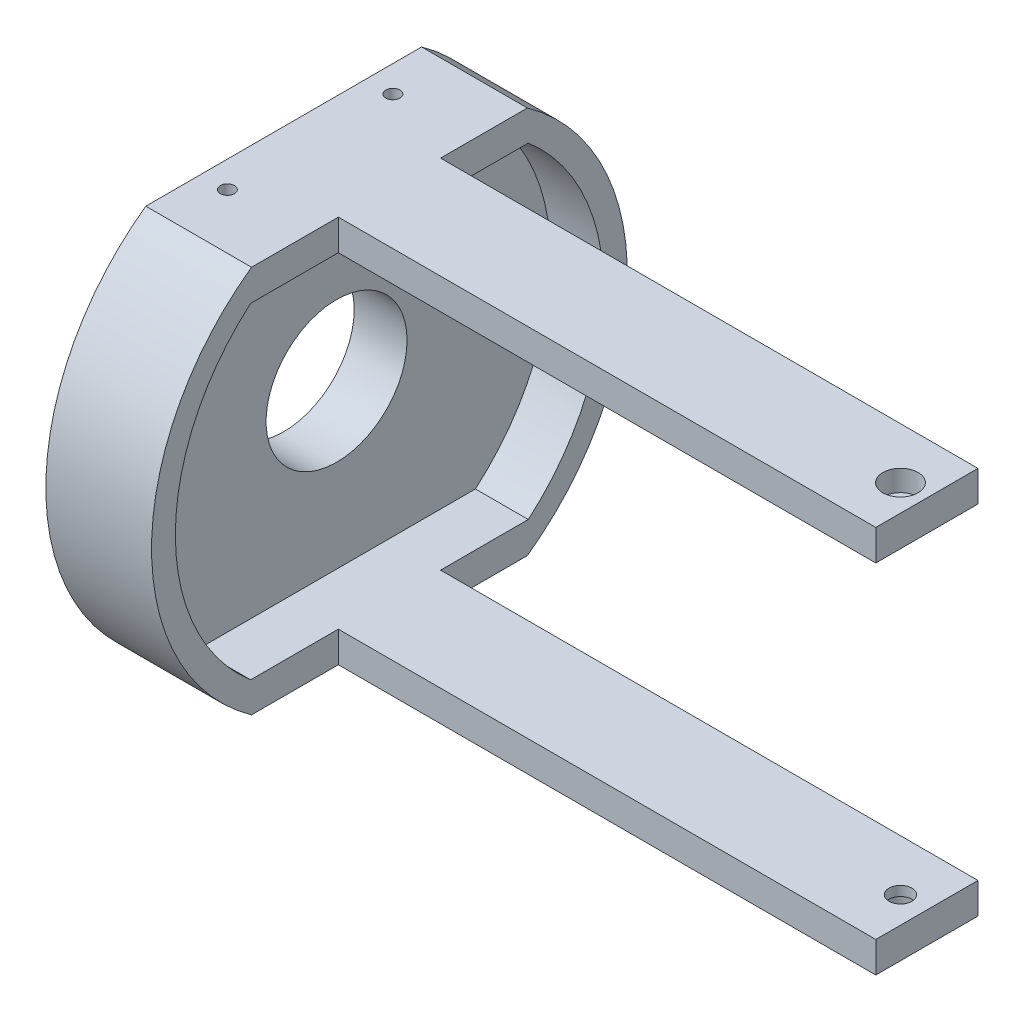
SolidWorks part; units mm, degrees
note: The reader was unsure of these and kept them because the rebuilt part matched: shared geometry of "草图3<4>", "草图3<5>", "草图3<6>".
ref_plane "前视基准面" through (0, 0, 0) normal (0, 0, 1) x (1, 0, 0)
ref_plane "上视基准面" through (0, 0, 0) normal (0, 1, 0) x (1, 0, 0)
ref_plane "右视基准面" through (0, 0, 0) normal (1, 0, 0) x (0, 0, -1)
other "Configuration Table"
sketch "草图1" plane through (0, 0, 0) normal (1, 0, 0) x (0, 0, -1)
  line L5 (-13.5, -11) -> (13.5, -11)
  line L6 (-13.5, -11) -> (-13.5, 11)
  line L7 (-13.5, 11) -> (13.5, 11)
  line L8 (13.5, -11) -> (13.5, 11)
  line L9 (-13.5, -11) -> (13.5, 11) construction
  line L10 (-13.5, 11) -> (13.5, -11) construction
  circle A0 centre (0, 0) radius 13.5
  circle A3 centre (0, 0) radius 4
  point P0 (0, 0)
  dimension "D1" = 27
  dimension "D6" = 8
  dimension "D3" = 22
extrude "凸台-拉伸1" add sketch "草图1" along normal blind 3 contours L7 A0 L5 A3
sketch "草图2" plane through (3, 0, 0) normal (1, 0, 0) x (0, 0, -1)
  line L1 (-12.15, -9.25) -> (12.15, -9.25)
  line L2 (-12.15, -9.25) -> (-12.15, 9.25)
  line L3 (-12.15, 9.25) -> (12.15, 9.25)
  line L4 (12.15, -9.25) -> (12.15, 9.25)
  line L5 (-12.15, -9.25) -> (12.15, 9.25) construction
  line L6 (-12.15, 9.25) -> (12.15, -9.25) construction
  circle A0 centre (0, 0) radius 12.15
  arc M7 (7.8262, -11) -> (7.8262, 11) centre (0, 0) ccw
  line M8 (7.8262, 11) -> (-7.8262, 11)
  arc M9 (-7.8262, 11) -> (-7.8262, -11) centre (0, 0) ccw
  line M10 (-7.8262, -11) -> (7.8262, -11)
  dimension "D1" = 24.3
  dimension "D2" = 18.5
extrude "凸台-拉伸2" add sketch "草图2" along normal blind 3 contours L3 A0 M8 | A0 L3 M8 M9 | A0 L3 L2 M9 | L2 M9 | A0 L2 L1 M9 | A0 L1 M9 M10 | L1 A0 M10 | A0 L1 M10 M7 | A0 L1 L4 M7 | L4 M7 | A0 L4 L3 M7 | A0 L3 M7 M8
sketch "草图3" plane through (0, 11, 0) normal (0, 1, 0) x (1, 0, 0)
  line L0 (0, -7.8262) -> (0, 7.8262) construction
  line L1 (0, -2.9) -> (36.5, -2.9)
  line L2 (0, -2.9) -> (0, 2.9)
  line L3 (0, 2.9) -> (36.5, 2.9)
  line L4 (36.5, -2.9) -> (36.5, 2.9)
  circle A0 centre (35, 0) radius 0.65
  circle A1 centre (35, 0) radius 1
  point P10 (0, 0)
  dimension "D3" = 1.3
  dimension "D4" = 2
  dimension "D1" = 5.8
  dimension "D2" = 36.5
extrude "凸台-拉伸3" add sketch "草图3" against normal up to surface (1.75 mm away) contours L3 L4 L1 L2 | A0 up to face at (4.5, 9.25, 0)
extrude "切除-拉伸1" cut sketch "草图3<4>" against normal blind 1.2 contours A1
sketch "草图3<4>" plane through (0, 11, 0) normal (0, 1, 0) x (1, 0, 0) same geometry as "草图3"
extrude "凸台-拉伸4" add sketch "草图3<5>" against normal up to surface (1.75 mm away) from surface contours L4 L3 L2 L1 | A0
sketch "草图3<5>" plane through (0, 11, 0) normal (0, 1, 0) x (1, 0, 0) same geometry as "草图3"
extrude "切除-拉伸2" cut sketch "草图3<6>" along normal blind 1.2 from surface at -22 contours A1 starting at face at (12.125, -11, 0)
sketch "草图3<6>" plane through (0, 11, 0) normal (0, 1, 0) x (1, 0, 0) same geometry as "草图3"
sketch "草图5" plane through (0, 11, 0) normal (0, 1, 0) x (1, 0, 0)
  line L1 (0, -7.8262) -> (0, 7.8262) construction
  line L2 (1.5, -7.8262) -> (1.5, -4.6957) construction
  line L3 (6, -7.8262) -> (0, -7.8262) construction
  line L4 (1.5, -4.6957) -> (1.5, -1.5652) construction
  line L5 (1.5, -1.5652) -> (1.5, 1.5652) construction
  line L6 (1.5, 4.6957) -> (1.5, 7.8262) construction
  line L7 (6, 7.8262) -> (0, 7.8262) construction
  line L8 (1.5, 1.5652) -> (1.5, 4.6957) construction
  circle A0 centre (1.5, -4.6957) radius 0.4
  circle A1 centre (1.5, 4.6957) radius 0.4
  dimension "D2" = 0.8
  dimension "D1" = 1.5
extrude "切除-拉伸3" cut sketch "草图5" against normal blind 2
